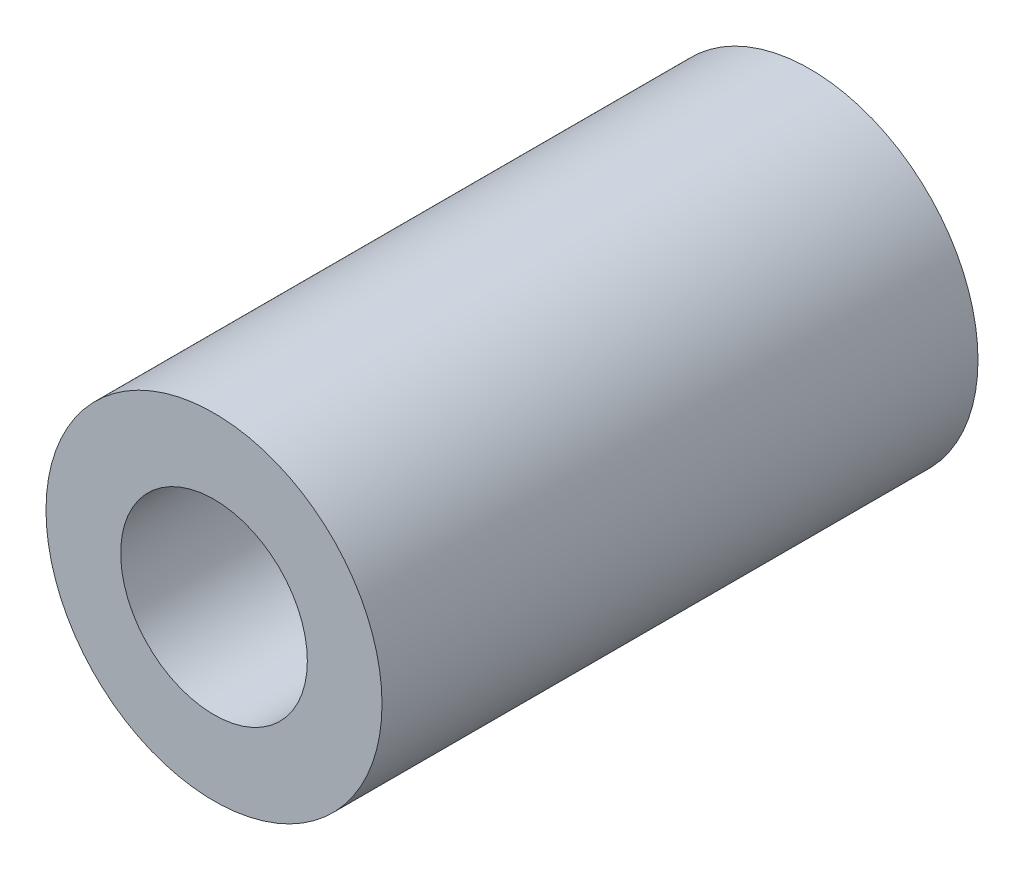
SolidWorks part; units mm, degrees
ref_plane "Front" through (0, 0, 0) normal (0, 0, 1) x (1, 0, 0)
ref_plane "Top" through (0, 0, 0) normal (0, 1, 0) x (1, 0, 0)
ref_plane "Right" through (0, 0, 0) normal (1, 0, 0) x (0, 0, -1)
sketch "Sketch1" plane through (0, 0, 0) normal (0, 0, 1) x (1, 0, 0)
  circle A0 centre (0, 0) radius 2.5
  circle A1 centre (0, 0) radius 4.5
extrude "Extrude1" add sketch "Sketch1" along normal blind 15.963
